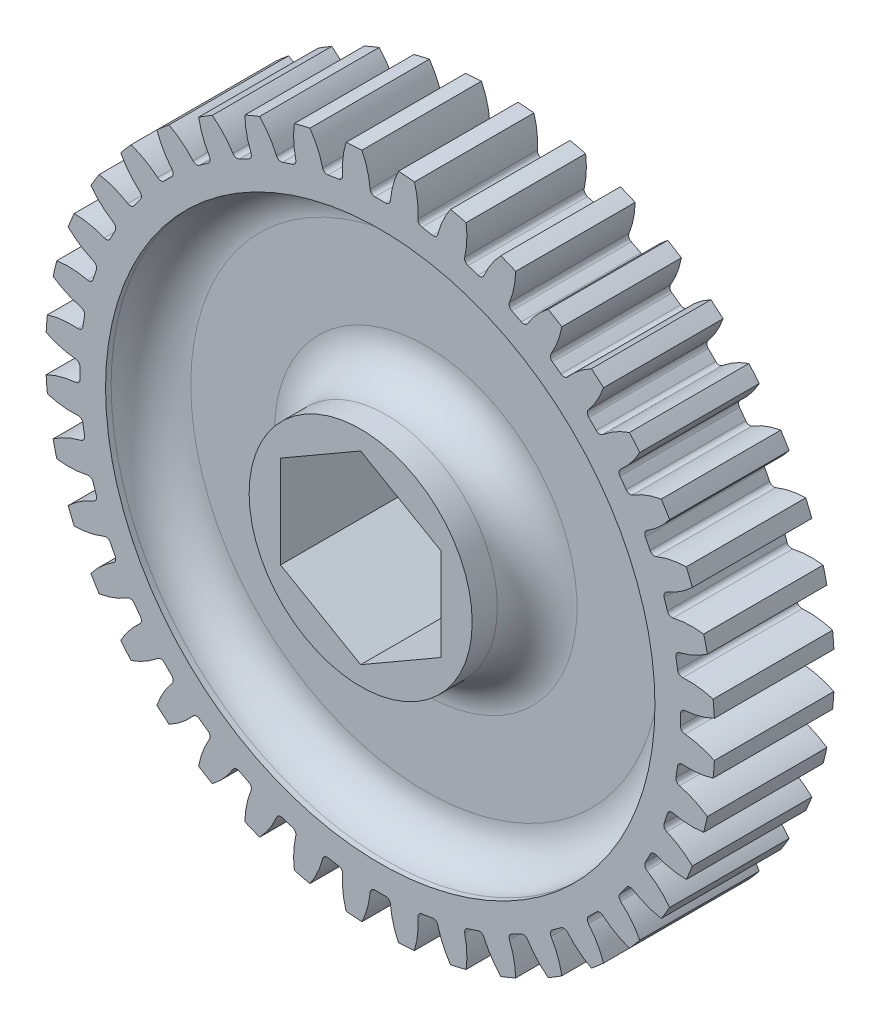
SolidWorks part; units mm, degrees
material "7075-T6 (SN)"
ref_plane "Alzado" through (0, 0, 0) normal (0, 0, 1) x (1, 0, 0)
ref_plane "Planta" through (0, 0, 0) normal (0, 1, 0) x (1, 0, 0)
ref_plane "Vista lateral" through (0, 0, 0) normal (1, 0, 0) x (0, 0, -1)
sketch "Croquis1" plane through (0, 0, 0) normal (0, 0, 1) x (1, 0, 0)
  circle A0 centre (0, 0) radius 25.4 construction
  circle A1 centre (0, 0) radius 26.67
  dimension "D" = 50.8
  dimension "OD" = 53.34
extrude "Saliente-Extruir1" add sketch "Croquis1" along normal mid plane 9.525
sketch "Croquis2" plane through (0, 0, 0) normal (0, 0, 1) x (1, 0, 0)
  line L0 (0, 0) -> (0, 26.67) construction
  line L1 (0, 0) -> (4.1721, 26.3416) construction
  line L2 (0, 0) -> (2.0925, 26.5878) construction
  line L3 (-0.7866, 23.9177) -> (0, 0) construction
  line L4 (-0.9972, 25.3804) -> (0.9972, 25.3804) construction
  line L5 (0.9972, 25.3804) -> (2.9854, 25.2239) construction
  line L6 (-1.3222, 26.6372) -> (0, 21.5245) construction
  circle A0 centre (0, 0) radius 26.67 construction
  arc A2 (0.7866, 23.9177) -> (-0.7866, 23.9177) centre (0, 0) ccw
  circle A5 centre (0, 0) radius 25.4 construction
  arc A6 (-1.4566, 26.6302) -> (-0.7866, 23.9177) centre (-7.508, 23.6966) cw
  arc A7 (1.4566, 26.6302) -> (0.7866, 23.9177) centre (7.508, 23.6966) ccw
  arc A8 (1.4566, 26.6302) -> (-1.4566, 26.6302) centre (0, 0) ccw
  dimension "D1" = 9
  dimension "D2" = 4.5
  dimension "B" = 1.4694
  dimension "Pressure Angle" = 14.5
extrude "Cortar-Extruir1" cut sketch "Croquis2" against normal through all both and the other way through all
fillet "Redondeo1" radius 0.381 2 edges at (0.7866, 23.9177, 0) (-0.7866, 23.9177, 0)
pattern_circular "MatrizC1" count 40 over 360 about axis through (0, 0, 4.7625) along (0, 0, -1) of "Cortar-Extruir1", "Redondeo1"
sketch "Croquis3" plane through (0, 0, 0) normal (0, 0, 1) x (1, 0, 0)
  circle A0 centre (0, 0) radius 8.89
  dimension "sp" = 17.78
extrude "Saliente-Extruir2" add sketch "Croquis3" along normal mid plane 12.6492
sketch "Croquis4" plane through (0, 0, 0) normal (0, 0, 1) x (1, 0, 0)
  line L1 (0, 7.3763) -> (-6.3881, 3.6882)
  line L2 (-6.3881, 3.6882) -> (-6.3881, -3.6882)
  line L3 (-6.3881, -3.6882) -> (0, -7.3763)
  line L4 (0, -7.3763) -> (6.3881, -3.6882)
  line L5 (6.3881, -3.6882) -> (6.3881, 3.6882)
  line L6 (6.3881, 3.6882) -> (0, 7.3763)
  circle A0 centre (0, 0) radius 6.3881 construction
  dimension "D1" = 12.7762
extrude "Cortar-Extruir2" cut sketch "Croquis4" against normal through all both and the other way through all
sketch "Croquis7" plane through (0, 0, 0) normal (0, 0, 1) x (1, 0, 0)
  circle A0 centre (0, 0) radius 21.8948
  circle A1 centre (0, 0) radius 8.89
  circle A5 centre (0, 0) radius 26.67 construction
  circle A6 centre (0, 0) radius 8.89 construction
  dimension "D1" = 4.7752
extrude "Cortar-Extruir5" cut sketch "Croquis7" against normal through all from offset 1.143 offset against normal yes
fillet "Redondeo2" radius 3.175 2 edges at (8.89, 0, -1.143) (21.8948, 0, -1.143)
mirror "Simetría1" about plane through (0, 0, 0) normal (0, 0, 1) of "Redondeo2", "Cortar-Extruir5"
equation "\"Number of teeth\"=40"
equation "\"Diametral Pitch\"= 20"
equation "\"Pressure Angle\"= 14.5"
equation "\"D@Croquis1\"=\"Number of teeth\"/\"Diametral Pitch\""
equation "\"OD@Croquis1\"=(\"Number of teeth\"+2) /\"Diametral Pitch\""
equation "\"D2@Croquis2\"=(360 / \"Number of teeth\")/ 2."
equation "\"D1@Croquis2\"=360 / \"Number of teeth\""
equation "\"B@Croquis2\"=1.157 / \"Diametral Pitch\""
equation "\"Pressure Angle@Croquis2\" = \"Pressure Angle\""
equation "\"D1@Redondeo1\"=(pi / \"Diametral Pitch\") * .0955"
equation "\"D1@MatrizC1\"=\"Number of teeth\""
equation "\"Tt@Saliente-Extruir1\"=if( \"Number of teeth\"=>30,0.375,0.475)"
equation "\"sp@Croquis3\"=if( \"Number of teeth\"=16,0.65,0.7)"
